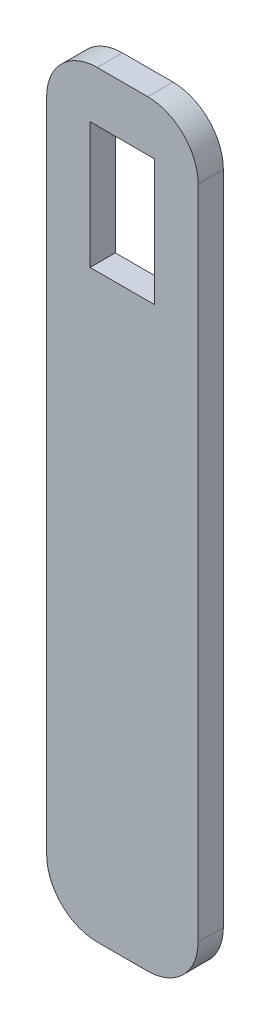
SolidWorks part; units mm, degrees
ref_plane "Přední rovina" through (0, 0, 0) normal (0, 0, 1) x (1, 0, 0)
ref_plane "Horní rovina" through (0, 0, 0) normal (0, 1, 0) x (1, 0, 0)
ref_plane "Pravá rovina" through (0, 0, 0) normal (1, 0, 0) x (0, 0, -1)
sketch "Skica1" plane through (0, 0, 0) normal (0, 0, 1) x (1, 0, 0)
  line L1 (0, 0) -> (30, 0)
  line L2 (0, 0) -> (0, 150)
  line L3 (0, 150) -> (30, 150)
  line L4 (30, 0) -> (30, 150)
  dimension "D1" = 150
  dimension "D2" = 30
extrude "Přidat vysunutím1" add sketch "Skica1" along normal blind 5
fillet "Zaoblit1" radius 10 4 edges at (30, 0, 2.5) (0, 0, 2.5) (30, 150, 2.5) (0, 150, 2.5)
sketch "Skica2" plane through (0, 0, 5) normal (0, 0, 1) x (1, 0, 0)
  line L1 (8.6, 140) -> (21.4, 140)
  line L2 (8.6, 140) -> (8.6, 115)
  line L3 (8.6, 115) -> (21.4, 115)
  line L4 (21.4, 140) -> (21.4, 115)
  line L5 (20, 150) -> (10, 150) construction
  point P4 (15, 150)
  point P7 (15, 140)
  dimension "D1" = 12.8
  dimension "D2" = 25
  dimension "D3" = 10
extrude "Odebrat vysunutím1" cut sketch "Skica2" against normal through all
